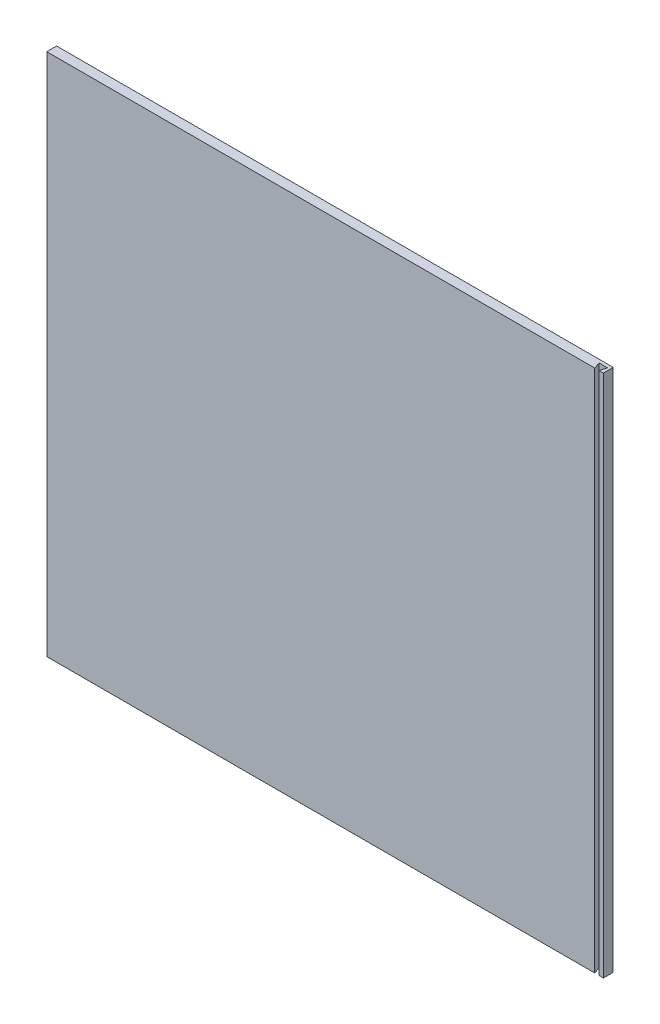
SolidWorks part; units mm, degrees
ref_plane "Front Plane" through (0, 0, 0) normal (0, 0, 1) x (1, 0, 0)
ref_plane "Top Plane" through (0, 0, 0) normal (0, 1, 0) x (1, 0, 0)
ref_plane "Right Plane" through (0, 0, 0) normal (1, 0, 0) x (0, 0, -1)
sketch "Sketch1" plane through (0, 0, 0) normal (0, 0, 1) x (1, 0, 0)
  line L1 (0, 0) -> (85, 0)
  line L2 (0, 0) -> (0, 80)
  line L3 (0, 80) -> (85, 80)
  line L4 (85, 0) -> (85, 80)
  dimension "D1" = 80
  dimension "D2" = 85
extrude "Boss-Extrude1" add sketch "Sketch1" along normal blind 1.5
sketch "Sketch2" plane through (0, 80, 0) normal (0, 1, 0) x (1, 0, 0)
  line L1 (84.65, -0.5) -> (85, -0.5) construction
  line L2 (85, -1.5) -> (85, 0) construction
  line L13 (83.35, -0.5) -> (84.65, -0.5)
  line L14 (83.35, -0.5) -> (83.675, -1.5)
  line L15 (84.325, -1.5) -> (83.675, -1.5)
  line L16 (84.65, -0.5) -> (84.325, -1.5)
  dimension "D1" = 0.35
extrude "Cut-Extrude1" cut sketch "Sketch2" against normal up to surface (80 mm away) up to face at (42.5, 0, 0.75)
